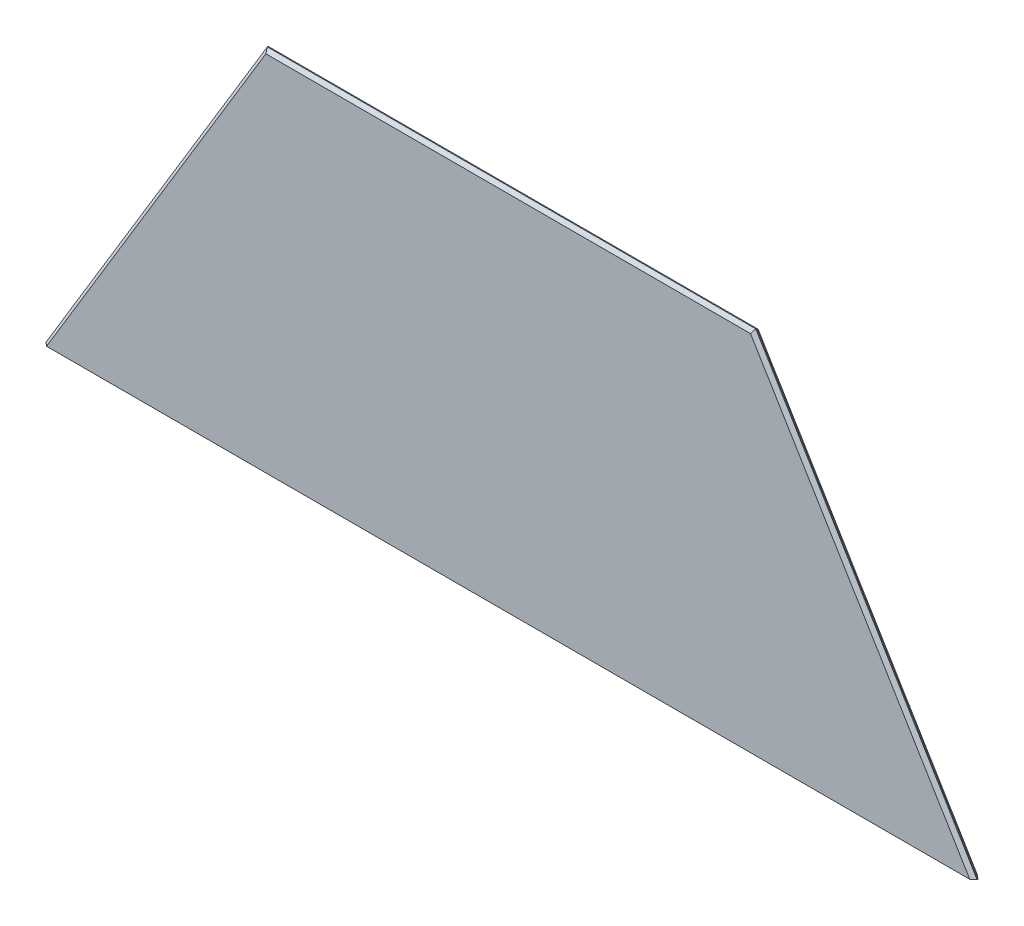
SolidWorks part; units mm, degrees
material "Printed Circuit Board"
ref_plane "Front Plane" through (0, 0, 0) normal (0, 0, 1) x (1, 0, 0)
ref_plane "Top Plane" through (0, 0, 0) normal (0, 1, 0) x (1, 0, 0)
ref_plane "Right Plane" through (0, 0, 0) normal (1, 0, 0) x (0, 0, -1)
sketch "Sketch1" plane through (0, 0, 0) normal (0, 0, 1) x (1, 0, 0)
  line L0 (0, 0) -> (193.675, 0)
  line L1 (193.675, 0) -> (101.6, 152.4)
  line L2 (101.6, 152.4) -> (0, 152.4)
  line L3 (0, 152.4) -> (-101.6, 152.4)
  line L4 (-101.6, 152.4) -> (-193.675, 0)
  line L5 (-193.675, 0) -> (0, 0)
  line L6 (0, 0) -> (0, 152.4) construction
  dimension "D1" = 152.4
  dimension "D2" = 387.35
  dimension "D3" = 203.2
extrude "Extrude1" add sketch "Sketch1" along normal mid plane 3.175
ref_plane "Plane1" through (0, 0, 0) normal (-1, 0, 0) x (0, 0, 1)
chamfer "Chamfer1" distance 1.397 angle 45 6 edges at (147.6375, 76.2, -1.5875) (0, 152.4, -1.5875) (-147.6375, 76.2, -1.5875) (147.6375, 76.2, 1.5875) (0, 152.4, 1.5875) (-147.6375, 76.2, 1.5875)
